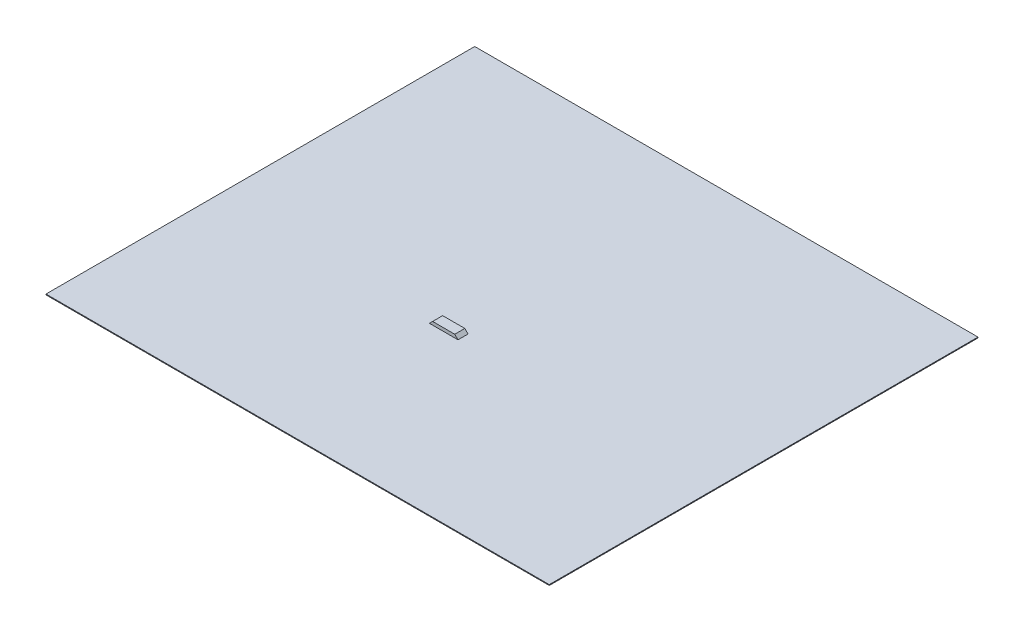
SolidWorks part; units mm, degrees
ref_plane "Front Plane" through (0, 0, 0) normal (0, 0, 1) x (1, 0, 0)
ref_plane "Top Plane" through (0, 0, 0) normal (0, 1, 0) x (1, 0, 0)
ref_plane "Right Plane" through (0, 0, 0) normal (1, 0, 0) x (0, 0, -1)
sketch "Sketch1" plane through (0, 0, 0) normal (0, 1, 0) x (1, 0, 0)
  line L5 (-2689.6908, 3127.0404) -> (3546.738, 3127.0404)
  line L6 (-2689.6908, 3127.0404) -> (-2689.6908, -2185.3915)
  line L7 (-2689.6908, -2185.3915) -> (3546.738, -2185.3915)
  line L8 (3546.738, 3127.0404) -> (3546.738, -2185.3915)
extrude "Boss-Extrude1" add sketch "Sketch1" along normal blind 10
sketch "Sketch2" plane through (0, 10, 0) normal (0, 1, 0) x (1, 0, 0)
  line L1 (354.4707, 0) -> (0, 0)
  line L2 (354.4707, 0) -> (354.4707, -124.3891)
  line L3 (354.4707, -124.3891) -> (0, -124.3891)
  line L4 (0, 0) -> (0, -124.3891)
extrude "Boss-Extrude2" add sketch "Sketch2" along normal blind 40
chamfer "Chamfer1" distance 40 2 edges at (354.4707, 50, 62.1946) (0, 50, 62.1946)
